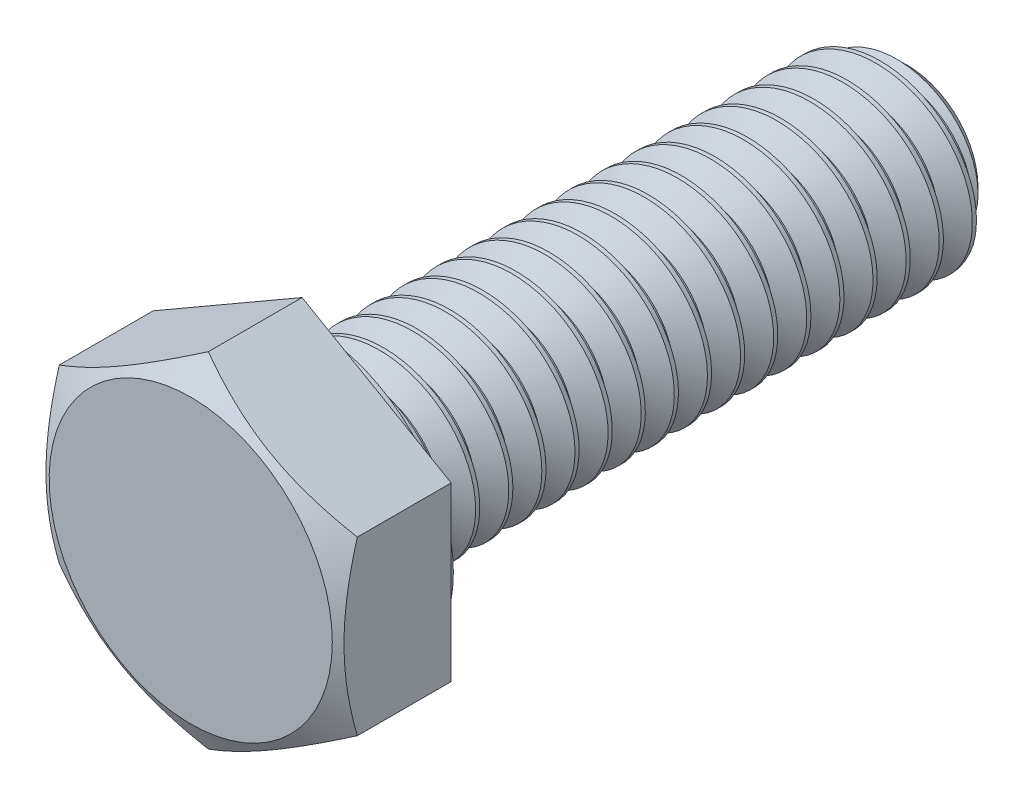
SolidWorks part; units mm, degrees
ref_plane "Front Plane" through (0, 0, 0) normal (0, 0, 1) x (1, 0, 0)
ref_plane "Top Plane" through (0, 0, 0) normal (0, 1, 0) x (1, 0, 0)
ref_plane "Right Plane" through (0, 0, 0) normal (1, 0, 0) x (0, 0, -1)
sketch "Sketch1" plane through (0, 0, 0) normal (1, 0, 0) x (0, 0, -1)
  line L0 (-15.2797, 0) -> (15.2797, 0) construction
  line L1 (15.2797, 3.9751) -> (15.2797, -3.9751) construction
  line L2 (-15.2797, 6.35) -> (-15.2797, -6.35) construction
  line L3 (-10.1203, -6.35) -> (-10.1203, 6.35) construction
  point P7 (13.8686, 0)
  point P10 (-10.1203, 0)
  point P11 (10.3408, -3.9751)
  point P12 (7.6597, 0)
  point P17 (-2.5003, 0)
  dimension "Length" = 25.4
  dimension "Head Height" = 5.1594
  dimension "Screw Size Decimal Equivalent" = 7.9502
  dimension "Head Width" = 12.7
  dimension "Thread Pitch" = 1.4111
  dimension "D1" = 4.9389
  dimension "D2" = 7.62
  dimension "D3" = 7.62
sketch "Sketch2" plane through (0, 0, 0) normal (0, 0, 1) x (1, 0, 0)
  line L1 (0, 7.3323) -> (-6.35, 3.6662) construction
  line L2 (-6.35, 3.6662) -> (-6.35, -3.6662) construction
  line L3 (-6.35, -3.6662) -> (0, -7.3323) construction
  line L4 (0, -7.3323) -> (6.35, -3.6662) construction
  line L5 (6.35, -3.6662) -> (6.35, 3.6662) construction
  line L6 (6.35, 3.6662) -> (0, 7.3323) construction
  circle A0 centre (0, 0) radius 6.35 construction
sketch "Sketch3" plane through (0, 0, 0) normal (1, 0, 0) x (0, 0, -1)
  line L0 (-15.2797, 0) -> (-15.2797, 6.0325)
  line L1 (-14.5292, 7.3323) -> (-10.5331, 7.3323)
  line L2 (-10.5331, 7.3323) -> (-10.5331, 6.0325)
  line L4 (-10.5331, 6.0325) -> (-10.1203, 6.0325)
  line L5 (-10.1203, 6.0325) -> (-10.1203, 3.9751)
  line L6 (-10.1203, 3.9751) -> (14.2919, 3.9751)
  line L7 (15.2797, 2.9873) -> (15.2797, 0)
  line L8 (-15.2797, 0) -> (15.2797, 0) construction
  line L9 (-15.2797, 6.0325) -> (-14.5292, 7.3323)
  line L10 (-15.2797, 0) -> (15.2797, 0)
  line L11 (-15.2797, 6.35) -> (-15.2797, -6.35) construction
  line L12 (-15.2797, 6.0325) -> (-10.5331, 6.0325) construction
  line L13 (-15.2797, 0) -> (-20.0263, 0) construction
  line L14 (14.2919, 3.9751) -> (15.2797, 2.9873)
  line L15 (-10.1203, -6.35) -> (-10.1203, 6.35) construction
  dimension "D2" = 30
  dimension "D3" = 12.065
  dimension "D4" = 45
  dimension "D5" = 0.9878
  dimension "D1" = 0.4127
revolve "Revolve1" add sketch "Sketch3" angle 360 about L0
sketch "Sketch4" plane through (0, 0, 15.2797) normal (0, 0, 1) x (1, 0, 0)
  line L0 (6.35, 3.6662) -> (0, 7.3323) construction
  line L1 (6.35, -3.6662) -> (6.35, 3.6662) construction
  line L2 (0, -7.3323) -> (6.35, -3.6662) construction
  line L3 (-6.35, -3.6662) -> (0, -7.3323) construction
  line L4 (-6.35, 3.6662) -> (-6.35, -3.6662) construction
  line L5 (0, 7.3323) -> (-6.35, 3.6662) construction
  line L6 (6.35, 3.6662) -> (0, 7.3323)
  line L7 (6.35, -3.6662) -> (6.35, 3.6662)
  line L8 (0, -7.3323) -> (6.35, -3.6662)
  line L9 (-6.35, -3.6662) -> (0, -7.3323)
  line L10 (-6.35, 3.6662) -> (-6.35, -3.6662)
  line L11 (0, 7.3323) -> (-6.35, 3.6662)
extrude "Cut-Extrude1" cut sketch "Sketch4" against normal through all flip side to cut
ref_plane "Plane1" through (0, 0, 10.1203) normal (0, 0, -1) x (-1, 0, 0)
split "Split1" trim tools "Plane1" bodies to split 105 resulting bodies 106 107
sketch "Sketch5" plane through (0, 0, -15.2797) normal (0, 0, -1) x (-1, 0, 0)
  circle A0 centre (0, 0) radius 3.9751
curve "Helix/Spiral1" pitch 1.4111 height 26.8111 turns 19
sketch "Sketch7" plane through (0, 0, 0) normal (1, 0, 0) x (0, 0, -1)
  line L0 (15.1915, 4.1279) -> (15.897, 2.9058) construction
  line L1 (15.897, 2.9058) -> (16.6026, 4.1279) construction
  line L2 (16.6026, 4.1279) -> (15.1915, 4.1279) construction
  line L3 (15.2797, 3.9751) -> (16.5144, 3.9751) construction
  line L4 (15.897, 4.1279) -> (15.897, 3.9751) construction
  line L5 (15.897, 3.9751) -> (15.897, 3.0586) construction
  line L6 (15.897, 3.0586) -> (15.897, 2.9058) construction
  line L7 (15.8089, 3.0586) -> (15.9852, 3.0586)
  line L8 (15.2356, 4.0515) -> (16.5585, 4.0515)
  line L9 (15.9852, 3.0586) -> (16.5585, 4.0515)
  line L10 (15.8089, 3.0586) -> (15.2356, 4.0515)
  point P12 (15.897, 4.0515)
  dimension "D1" = 1.4111
  dimension "D2" = 0.1764
sweep "Cut-Sweep1" cut profiles "Sketch7" path "Helix/Spiral1" align with end faces yes
sketch "Sketch11" plane through (0, 0, 10.1203) normal (0, 0, 1) x (1, 0, 0)
  circle A1 centre (0, 0) radius 3.9751
extrude "Boss-Extrude2" add sketch "Sketch11" against normal through all draft 30
equation "\"D3@Sketch3\"=\"Head Width@Sketch1\"*0.95"
equation "\"D5@Sketch3\"=\"Thread Pitch@Sketch1\"*0.7"
equation "\"D4@Helix/Spiral1\"=\"Thread Pitch@Sketch1\""
equation "\"D3@Helix/Spiral1\"=\"Length@Sketch1\"+\"Thread Pitch@Sketch1\""
equation "\"D2@Sketch7\"=\"D1@Sketch7\"/8"
equation "\"D1@Sketch7\"=\"Thread Pitch@Sketch1\""
equation "\"D1@Sketch3\"=\"Head Height@Sketch1\"*0.08"
equation "\"D1@Sketch1\"=\"Thread Pitch@Sketch1\"*3.5"
equation "\"D2@Sketch1\"=\"Length@Sketch1\"*0.3"
equation "\"D3@Sketch1\"=\"D2@Sketch1\""
